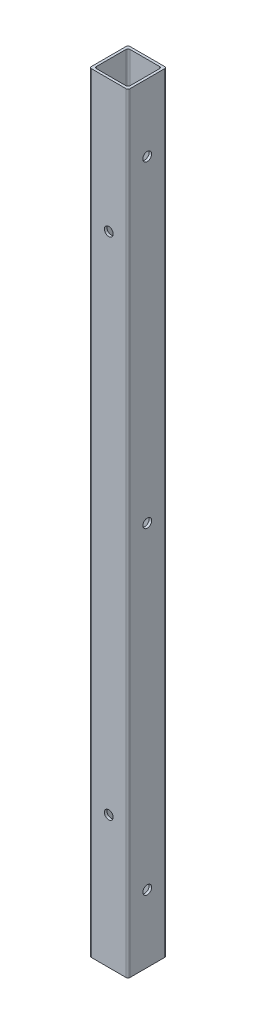
SolidWorks part; units mm, degrees
ref_plane "Front Plane" through (0, 0, 0) normal (0, 0, 1) x (1, 0, 0)
ref_plane "Top Plane" through (0, 0, 0) normal (0, 1, 0) x (1, 0, 0)
ref_plane "Right Plane" through (0, 0, 0) normal (1, 0, 0) x (0, 0, -1)
sketch "Sketch1" plane through (0, 0, 0) normal (0, 1, 0) x (1, 0, 0)
  line L0 (11.049, -11.049) -> (11.049, 11.049)
  line L1 (-12.7, -12.7) -> (12.7, -12.7)
  line L2 (-12.7, -12.7) -> (-12.7, 12.7)
  line L3 (-12.7, 12.7) -> (12.7, 12.7)
  line L4 (12.7, -12.7) -> (12.7, 12.7)
  line L5 (-12.7, -12.7) -> (12.7, 12.7) construction
  line L6 (-12.7, 12.7) -> (12.7, -12.7) construction
  line L7 (-11.049, 11.049) -> (11.049, 11.049)
  line L8 (-11.049, -11.049) -> (-11.049, 11.049)
  line L9 (-11.049, -11.049) -> (11.049, -11.049)
  point P0 (0, 0)
  dimension "D1" = 25.4
  dimension "D2" = 1.651
extrude "Boss-Extrude1" add sketch "Sketch1" along normal blind 508
fillet "Fillet1" radius 1.27 8 edges at (-12.7, 254, 12.7) (-12.7, 254, -12.7) (12.7, 254, -12.7) (12.7, 254, 12.7) (-11.049, 254, -11.049) (11.049, 254, 11.049) (11.049, 254, -11.049) (-11.049, 254, 11.049)
hole_wizard "#1 (0.228) Diameter Hole2" positions "Sketch4" profile "Sketch5" hole size "#1" standard "ANSI Inch" end condition through all
sketch "Sketch4" plane through (-12.7, 0, 0) normal (-1, 0, 0) x (0, 0, 1)
  line L0 (0, 0) -> (0, 508) construction
  line L1 (-11.43, 0) -> (11.43, 0) construction
  line L2 (-11.43, 508) -> (11.43, 508) construction
  point P8 (0, 44.45)
  point P34 (0, 254)
  point P35 (0, 463.55)
  dimension "D1" = 44.45
  dimension "D2" = 3
sketch "Sketch5" plane through (-12.7, 463.55, 0) normal (0, 1, 0) x (0, 0, 1)
  line L0 (0, 0) -> (0, 25.4)
  line L1 (0, 25.4) -> (2.8956, 25.4)
  line L2 (2.8956, 25.4) -> (2.8956, 0)
  line L5 (2.8956, 0) -> (0, 0)
  line L11 (0, -6.35) -> (0, 107.95) construction
  dimension "Thru Hole Dia." = 5.7912
  dimension "Thru Hole Depth" = 25.4
hole_wizard "#1 (0.228) Diameter Hole3" positions "Sketch6" profile "Sketch7" hole size "#1" standard "ANSI Inch" end condition through all
sketch "Sketch6" plane through (0, 0, -12.7) normal (0, 0, -1) x (-1, 0, 0)
  line L0 (0, 508) -> (0, 0) construction
  line L1 (-11.43, 508) -> (11.43, 508) construction
  point P8 (0, 87.3125)
  point P10 (0, 420.6875)
  dimension "D1" = 87.3125
  dimension "D2" = 333.375
sketch "Sketch7" plane through (0, 420.6875, -12.7) normal (1, 0, 0) x (0, 1, 0)
  line L0 (0, 0) -> (0, 25.4)
  line L1 (0, 25.4) -> (2.8956, 25.4)
  line L2 (2.8956, 25.4) -> (2.8956, 0)
  line L5 (2.8956, 0) -> (0, 0)
  line L11 (0, -6.35) -> (0, 107.95) construction
  dimension "Thru Hole Dia." = 5.7912
  dimension "Thru Hole Depth" = 25.4
